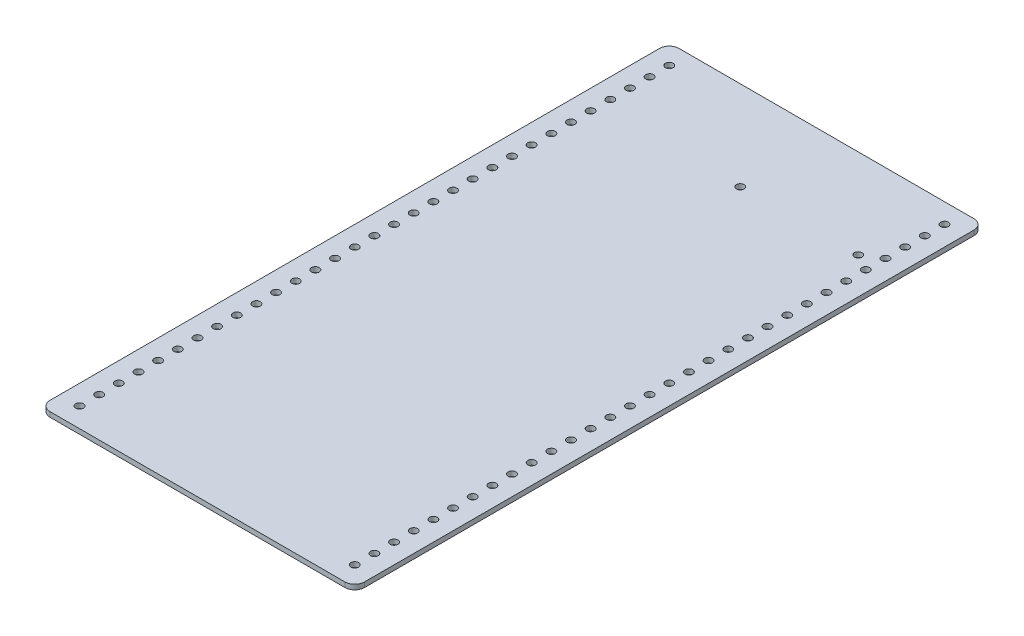
SolidWorks part; units mm, degrees
ref_plane "Front Plane" through (0, 0, 0) normal (0, 0, 1) x (1, 0, 0)
ref_plane "Top Plane" through (0, 0, 0) normal (0, 1, 0) x (1, 0, 0)
ref_plane "Right Plane" through (0, 0, 0) normal (1, 0, 0) x (0, 0, -1)
sketch "Sketch1" plane through (0, 0, 0) normal (0, 1, 0) x (1, 0, 0)
  line L1 (-77.8898, 288.009) -> (112.6102, 288.009)
  line L2 (-84.2398, 281.659) -> (-84.2398, -112.041)
  line L3 (-77.8898, -118.391) -> (112.6102, -118.391)
  line L4 (118.9602, 281.659) -> (118.9602, -112.041)
  arc A0 (-84.2398, -112.041) -> (-77.8898, -118.391) centre (-77.8898, -112.041) ccw
  arc A1 (112.6102, -118.391) -> (118.9602, -112.041) centre (112.6102, -112.041) ccw
  arc A2 (112.6102, 288.009) -> (118.9602, 281.659) centre (112.6102, 281.659) cw
  arc A3 (-77.8898, 288.009) -> (-84.2398, 281.659) centre (-77.8898, 281.659) ccw
  point P6 (-84.2398, -118.391)
  point P9 (118.9602, -118.391)
  point P14 (-84.2398, 288.009)
  dimension "D3" = 6.35
  dimension "D1" = 203.2
  dimension "D2" = 406.4
extrude "Boss-Extrude1" add sketch "Sketch1" along normal blind 3.175
sketch "Sketch3" plane through (0, 3.175, 0) normal (0, 1, 0) x (1, 0, 0)
  line L0 (118.9602, -112.041) -> (118.9602, 281.659) construction
  line L1 (112.6102, 288.009) -> (-77.8898, 288.009) construction
  line L2 (-84.2398, 281.659) -> (-84.2398, -112.041) construction
  circle A0 centre (-71.5398, 275.309) radius 2.5
  circle A1 centre (106.2602, 275.309) radius 2.5
  circle A2 centre (-71.5398, 262.609) radius 2.5
  circle A3 centre (106.2602, 262.609) radius 2.5
  circle A4 centre (-71.5398, 249.909) radius 2.5
  circle A5 centre (106.2602, 249.909) radius 2.5
  circle A6 centre (-71.5398, 237.209) radius 2.5
  circle A7 centre (106.2602, 237.209) radius 2.5
  circle A8 centre (-71.5398, 224.509) radius 2.5
  circle A9 centre (106.2602, 224.509) radius 2.5
  circle A10 centre (-71.5398, 211.809) radius 2.5
  circle A11 centre (106.2602, 211.809) radius 2.5
  circle A12 centre (-71.5398, 199.109) radius 2.5
  circle A13 centre (106.2602, 199.109) radius 2.5
  circle A14 centre (-71.5398, 186.409) radius 2.5
  circle A15 centre (106.2602, 186.409) radius 2.5
  circle A16 centre (-71.5398, 173.709) radius 2.5
  circle A17 centre (106.2602, 173.709) radius 2.5
  circle A18 centre (-71.5398, 161.009) radius 2.5
  circle A19 centre (106.2602, 161.009) radius 2.5
  circle A20 centre (-71.5398, 148.309) radius 2.5
  circle A21 centre (106.2602, 148.309) radius 2.5
  circle A22 centre (-71.5398, 135.609) radius 2.5
  circle A23 centre (106.2602, 135.609) radius 2.5
  circle A24 centre (-71.5398, 122.909) radius 2.5
  circle A25 centre (106.2602, 122.909) radius 2.5
  circle A26 centre (-71.5398, 110.209) radius 2.5
  circle A27 centre (106.2602, 110.209) radius 2.5
  circle A28 centre (-71.5398, 97.509) radius 2.5
  circle A29 centre (106.2602, 97.509) radius 2.5
  circle A30 centre (-71.5398, 84.809) radius 2.5
  circle A31 centre (106.2602, 84.809) radius 2.5
  circle A32 centre (-71.5398, 72.109) radius 2.5
  circle A33 centre (106.2602, 72.109) radius 2.5
  circle A34 centre (-71.5398, 59.409) radius 2.5
  circle A35 centre (106.2602, 59.409) radius 2.5
  circle A36 centre (-71.5398, 46.709) radius 2.5
  circle A37 centre (106.2602, 46.709) radius 2.5
  circle A38 centre (-71.5398, 34.009) radius 2.5
  circle A39 centre (106.2602, 34.009) radius 2.5
  circle A40 centre (-71.5398, 21.309) radius 2.5
  circle A41 centre (106.2602, 21.309) radius 2.5
  circle A42 centre (-71.5398, 8.609) radius 2.5
  circle A43 centre (106.2602, 8.609) radius 2.5
  circle A44 centre (-71.5398, -4.091) radius 2.5
  circle A45 centre (106.2602, -4.091) radius 2.5
  circle A46 centre (-71.5398, -16.791) radius 2.5
  circle A47 centre (106.2602, -16.791) radius 2.5
  circle A48 centre (-71.5398, -29.491) radius 2.5
  circle A49 centre (106.2602, -29.491) radius 2.5
  circle A50 centre (-71.5398, -42.191) radius 2.5
  circle A51 centre (106.2602, -42.191) radius 2.5
  circle A52 centre (-71.5398, -54.891) radius 2.5
  circle A53 centre (106.2602, -54.891) radius 2.5
  circle A54 centre (-71.5398, -67.591) radius 2.5
  circle A55 centre (106.2602, -67.591) radius 2.5
  circle A56 centre (-71.5398, -80.291) radius 2.5
  circle A57 centre (106.2602, -80.291) radius 2.5
  circle A58 centre (-71.5398, -92.991) radius 2.5
  circle A59 centre (106.2602, -92.991) radius 2.5
  circle A60 centre (-71.5398, -105.691) radius 2.5
  circle A61 centre (106.2602, -105.691) radius 2.5
  dimension "D1" = 5
  dimension "D2" = 5
  dimension "D3" = 12.7
  dimension "D4" = 12.7
  dimension "D5" = 12.7
  dimension "D6" = 12.7
  dimension "D7" = 31
extrude "Cut-Extrude2" cut sketch "Sketch3" against normal through all
sketch "Sketch7" plane through (0, 3.175, 0) normal (0, 1, 0) x (1, 0, 0)
  circle A0 centre (95.4796, 230.3677) radius 2.5 construction
  circle A1 centre (19.2796, 230.3677) radius 2.5 construction
  circle A2 centre (95.4796, 230.3677) radius 2.5
  circle A3 centre (19.2796, 230.3677) radius 2.5
extrude "Cut-Extrude5" cut sketch "Sketch7" against normal through all
